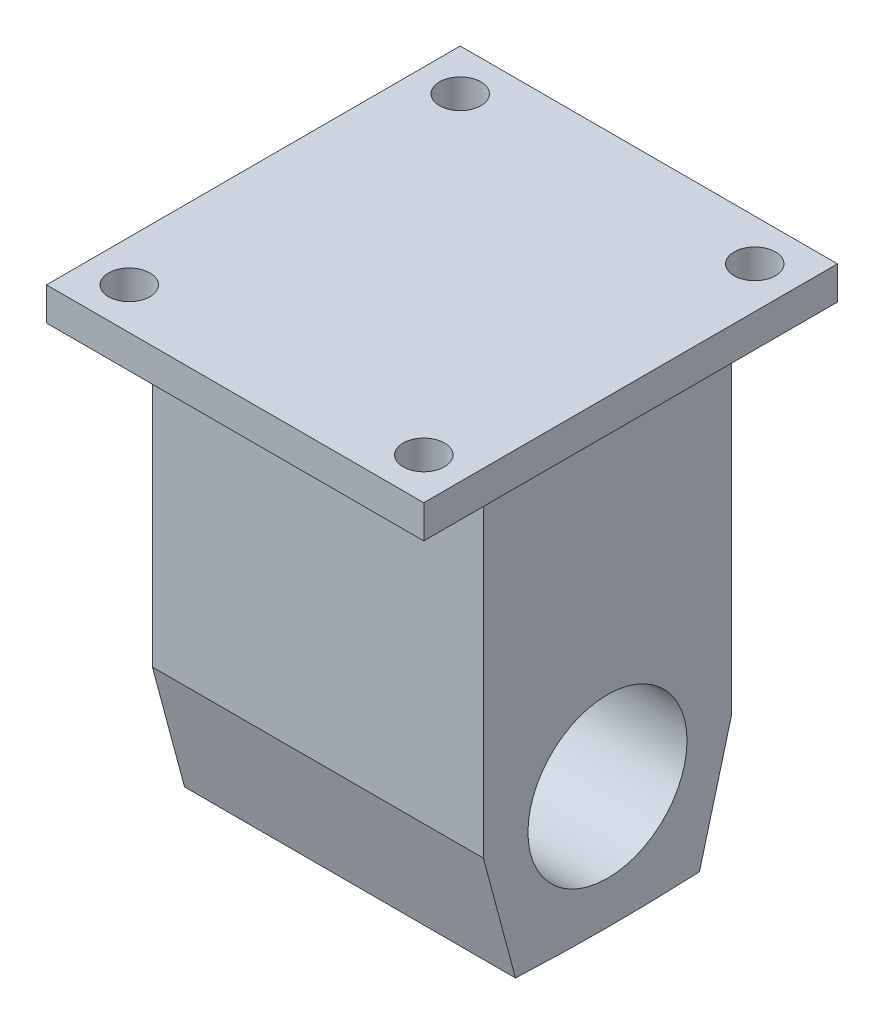
SolidWorks part; units mm, degrees
material "ABS"
ref_plane "Front Plane" through (0, 0, 0) normal (0, 0, 1) x (1, 0, 0)
ref_plane "Top Plane" through (0, 0, 0) normal (0, 1, 0) x (1, 0, 0)
ref_plane "Right Plane" through (0, 0, 0) normal (1, 0, 0) x (0, 0, -1)
sketch "Sketch1" plane through (0, 0, 0) normal (0, 1, 0) x (1, 0, 0)
  line L1 (-25.4, -19.05) -> (25.4, -19.05)
  line L2 (-25.4, -19.05) -> (-25.4, 19.05)
  line L3 (-25.4, 19.05) -> (25.4, 19.05)
  line L4 (25.4, -19.05) -> (25.4, 19.05)
  line L5 (-25.4, -19.05) -> (25.4, 19.05) construction
  line L6 (-25.4, 19.05) -> (25.4, -19.05) construction
  point P0 (0, 0)
extrude "Boss-Extrude1" add sketch "Sketch1" along normal blind 50.292
sketch "Sketch2" plane through (25.4, 0, 0) normal (1, 0, 0) x (0, 0, -1)
  line L0 (-19.05, 0) -> (-14.1195, -18.4009)
  line L1 (19.05, 0) -> (14.1195, -18.4009)
  line L2 (-19.05, 0) -> (19.05, 0)
  line L3 (-19.05, 0) -> (19.05, 0) construction
  arc A1 (14.1195, -18.4009) -> (-14.1195, -18.4009) centre (0, 281.2546) cw
  dimension "D1" = 19.05
  dimension "D2" = 19.05
  dimension "D3" = 75
  dimension "D4" = 75
extrude "Boss-Extrude2" add sketch "Sketch2" against normal up to vertex (50.8 mm away) contours L0 A1 L1 L2 up to point (-25.4, 0, -19.05)
sketch "Sketch3" plane through (25.4, 0, 0) normal (1, 0, 0) x (0, 0, -1)
  circle A0 centre (0, 0) radius 12.2085
extrude "Cut-Extrude1" cut sketch "Sketch3" against normal blind 127 contours A0
sketch "Sketch4" plane through (0, 50.292, 0) normal (0, 1, 0) x (1, 0, 0)
  line L1 (28.956, -31.75) -> (-28.956, -31.75)
  line L2 (28.956, -31.75) -> (28.956, 31.75)
  line L3 (28.956, 31.75) -> (-28.956, 31.75)
  line L4 (-28.956, -31.75) -> (-28.956, 31.75)
  line L5 (28.956, -31.75) -> (-28.956, 31.75) construction
  line L6 (28.956, 31.75) -> (-28.956, -31.75) construction
  point P0 (0, 0)
extrude "Boss-Extrude3" add sketch "Sketch4" along normal blind 5.08
sketch "Sketch5" plane through (0, 55.372, 0) normal (0, 1, 0) x (1, 0, 0)
  line L0 (0, -31.75) -> (0, 31.75) construction
  line L1 (28.956, 31.75) -> (-28.956, 31.75) construction
  line L2 (-28.956, 0) -> (28.956, 0) construction
  line L3 (28.956, -31.75) -> (28.956, 31.75) construction
  line L4 (-22.606, -31.75) -> (-22.606, 31.75) construction
  line L5 (-28.956, 25.4) -> (28.956, 25.4) construction
  line L6 (-28.956, 31.75) -> (-28.956, -31.75) construction
  circle A0 centre (-22.606, 25.4) radius 3.175
  circle A1 centre (-22.606, -25.4) radius 3.175
  circle A2 centre (22.606, 25.4) radius 3.175
  circle A3 centre (22.606, -25.4) radius 3.175
  point P6 (0, 0)
  point P12 (0, 0)
  point P15 (-22.606, 0)
  point P18 (0, 25.4)
  point P20 (-22.606, 25.4)
  dimension "D1" = 6.35
  dimension "D2" = 6.35
  dimension "D3" = 0
extrude "Cut-Extrude2" cut sketch "Sketch5" against normal blind 5.08
